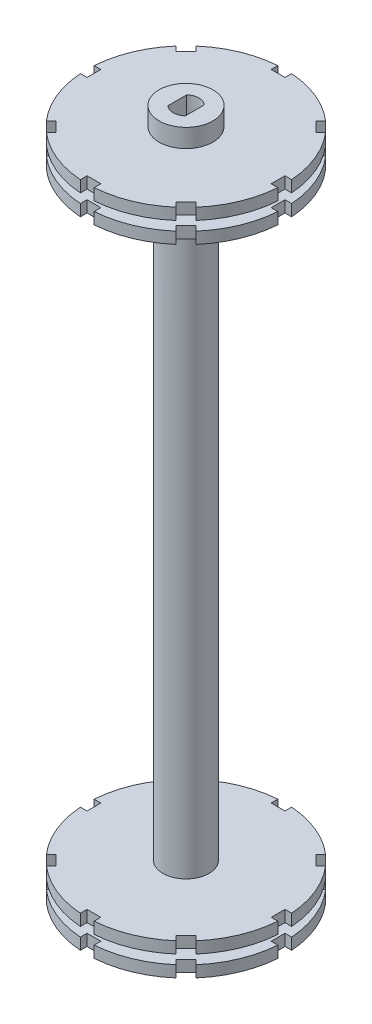
SolidWorks part; units mm, degrees
note: '?' marks a value the reader was unsure of.
ref_plane "Front Plane" through (0, 0, 0) normal (0, 0, 1) x (1, 0, 0)
ref_plane "Top Plane" through (0, 0, 0) normal (0, 1, 0) x (1, 0, 0)
ref_plane "Right Plane" through (0, 0, 0) normal (1, 0, 0) x (0, 0, -1)
sketch "Sketch1" plane through (0, 0, 0) normal (0, 1, 0) x (1, 0, 0)
  line L0 (1.9, 2.0567) -> (1.9, -2.0567)
  line L1 (-1.9, -2.0567) -> (-1.9, 2.0567)
  line L2 (-1.9, 2.0567) -> (-1.9, 5.5329)
  line L3 (1.9, 2.0567) -> (1.9, 5.5329)
  line L4 (-1.9, -2.0567) -> (-1.9, -5.5329)
  line L5 (1.9, -2.0567) -> (1.9, -5.5329)
  circle A0 centre (0, 0) radius 2.8
  circle A1 centre (0, 0) radius 5.85
  dimension "D1" = 5.6
  dimension "D4" = 11.7
  dimension "D2" = 1.9
  dimension "D3" = 1.9
extrude "Boss-Extrude1" add sketch "Sketch1" along normal blind 6.5 contours L2 A1 L4 A0 | L3 A1 L2 A0 | L5 A1 L3 A0 | L4 A1 L5 A0 | L1 A0 | L0 A0
sketch "Sketch2" plane through (0, 6.5, 0) normal (0, 1, 0) x (1, 0, 0)
  circle A0 centre (0, 0) radius 21.5
  dimension "D1" = 43
extrude "Boss-Extrude2" add sketch "Sketch2" against normal blind 2.5
sketch "Sketch3" plane through (0, 4, 0) normal (0, -1, 0) x (1, 0, 0)
  line L2 (-1.9, 2.0567) -> (-1.9, -2.0567)
  line L3 (1.9, -2.0567) -> (1.9, 2.0567)
  line L4 (-1.9, 2.0567) -> (-1.9, -2.0567)
  line L5 (1.9, -2.0567) -> (1.9, 2.0567)
  arc A2 (1.9, 2.0567) -> (-1.9, 2.0567) centre (0, 0) ccw
  arc A3 (-1.9, -2.0567) -> (1.9, -2.0567) centre (0, 0) ccw
  arc A4 (1.9, 2.0567) -> (-1.9, 2.0567) centre (0, 0) ccw
  arc A5 (-1.9, -2.0567) -> (1.9, -2.0567) centre (0, 0) ccw
  dimension "D1" = 0
extrude "Cut-Extrude1" cut sketch "Sketch3" against normal blind 8
sketch "Sketch4" plane through (0, 6.5, 0) normal (0, 1, 0) x (1, 0, 0)
  line L5 (15.2028, -13.0815) -> (17.3241, -15.2028)
  line L6 (15.2028, -13.0815) -> (13.0815, -15.2028)
  line L9 (20, 1.5) -> (23, 1.5)
  line L10 (20, 1.5) -> (20, -1.5)
  line L11 (20, -1.5) -> (23, -1.5)
  line L12 (23, 1.5) -> (23, -1.5)
  line L13 (20, 1.5) -> (23, -1.5) construction
  line L14 (20, -1.5) -> (23, 1.5) construction
  line L36 (13.0815, -15.2028) -> (15.2028, -17.3241)
  line L41 (17.3241, -15.2028) -> (15.2028, -17.3241)
  line L42 (15.2028, -13.0815) -> (15.2028, -17.3241) construction
  line L47 (13.0815, -15.2028) -> (17.3241, -15.2028) construction
  line L48 (1.5, -20) -> (1.5, -23)
  line L49 (1.5, -20) -> (-1.5, -20)
  line L54 (-1.5, -20) -> (-1.5, -23)
  line L55 (1.5, -23) -> (-1.5, -23)
  line L56 (1.5, -20) -> (-1.5, -23) construction
  line L61 (-1.5, -20) -> (1.5, -23) construction
  line L62 (-13.0815, -15.2028) -> (-15.2028, -17.3241)
  line L63 (-13.0815, -15.2028) -> (-15.2028, -13.0815)
  line L68 (-15.2028, -13.0815) -> (-17.3241, -15.2028)
  line L69 (-15.2028, -17.3241) -> (-17.3241, -15.2028)
  line L70 (-13.0815, -15.2028) -> (-17.3241, -15.2028) construction
  line L71 (-15.2028, -13.0815) -> (-15.2028, -17.3241) construction
  line L72 (-20, -1.5) -> (-23, -1.5)
  line L73 (-20, -1.5) -> (-20, 1.5)
  line L74 (-20, 1.5) -> (-23, 1.5)
  line L75 (-23, -1.5) -> (-23, 1.5)
  line L76 (-20, -1.5) -> (-23, 1.5) construction
  line L77 (-20, 1.5) -> (-23, -1.5) construction
  line L78 (-15.2028, 13.0815) -> (-17.3241, 15.2028)
  line L79 (-15.2028, 13.0815) -> (-13.0815, 15.2028)
  line L80 (-13.0815, 15.2028) -> (-15.2028, 17.3241)
  line L81 (-17.3241, 15.2028) -> (-15.2028, 17.3241)
  line L82 (-15.2028, 13.0815) -> (-15.2028, 17.3241) construction
  line L83 (-13.0815, 15.2028) -> (-17.3241, 15.2028) construction
  line L84 (-1.5, 20) -> (-1.5, 23)
  line L85 (-1.5, 20) -> (1.5, 20)
  line L86 (1.5, 20) -> (1.5, 23)
  line L87 (-1.5, 23) -> (1.5, 23)
  line L88 (-1.5, 20) -> (1.5, 23) construction
  line L89 (1.5, 20) -> (-1.5, 23) construction
  line L90 (13.0815, 15.2028) -> (15.2028, 17.3241)
  line L91 (13.0815, 15.2028) -> (15.2028, 13.0815)
  line L92 (15.2028, 13.0815) -> (17.3241, 15.2028)
  line L93 (15.2028, 17.3241) -> (17.3241, 15.2028)
  line L94 (13.0815, 15.2028) -> (17.3241, 15.2028) construction
  line L95 (15.2028, 13.0815) -> (15.2028, 17.3241) construction
  circle A0 centre (0, 0) radius 21.5 construction
  point P2 (15.2028, -15.2028)
  point P8 (0, -21.5)
  point P12 (21.5, 0)
  point P19 (-15.2028, -15.2028)
  point P24 (-21.5, 0)
  point P29 (-15.2028, 15.2028)
  point P34 (0, 21.5)
  point P39 (15.2028, 15.2028)
  dimension "D1" = 8
  dimension "D4" = 3
  dimension "D5" = 3
ref_axis "Axis1" through (0, 6.5, 0) along (0, -1, 0)?
extrude "Cut-Extrude2" cut sketch "Sketch4" against normal blind 10
sketch "Sketch5" plane through (0, 6.5, 0) normal (0, 1, 0) x (1, 0, 0)
  circle A0 centre (0, 0) radius 5
  dimension "D1" = 10
extrude "Boss-Extrude3" add sketch "Sketch5" along normal blind 140
ref_plane "Plane1" through (0, 76.5, 0) normal (0, 1, 0) x (1, 0, 0)
mirror "Mirror1" about plane through (0, 76.5, 0) normal (0, 1, 0) of "Boss-Extrude2"
mirror "Mirror2" about plane through (0, 76.5, 0) normal (0, 1, 0) of "Boss-Extrude1"
ref_plane "Plane2" through (0, 7.5, 0) normal (0, 1, 0) x (1, 0, 0)
mirror "Mirror3" about plane through (0, 7.5, 0) normal (0, 1, 0) of "Cut-Extrude2", "Boss-Extrude2", "Cut-Extrude1"
sketch "Sketch6" plane through (0, 11, 0) normal (0, -1, 0) x (1, 0, 0)
  line L2 (-1.9, 2.0567) -> (-1.9, -2.0567)
  line L3 (1.9, -2.0567) -> (1.9, 2.0567)
  line L4 (-1.9, 2.0567) -> (-1.9, -2.0567)
  line L5 (1.9, -2.0567) -> (1.9, 2.0567)
  arc A2 (1.9, 2.0567) -> (-1.9, 2.0567) centre (0, 0) ccw
  arc A3 (-1.9, -2.0567) -> (1.9, -2.0567) centre (0, 0) ccw
  arc A4 (1.9, 2.0567) -> (-1.9, 2.0567) centre (0, 0) ccw
  arc A5 (-1.9, -2.0567) -> (1.9, -2.0567) centre (0, 0) ccw
  dimension "D1" = 0
extrude "Cut-Extrude3" cut sketch "Sketch6" against normal blind 15
ref_plane "Plane3" through (0, 145.5, 0) normal (0, -1, 0) x (-1, 0, 0)
mirror "Mirror5" about plane through (0, 76.5, 0) normal (0, 1, 0) of "Cut-Extrude2"
mirror "Mirror6" about plane through (0, 145.5, 0) normal (0, -1, 0) of "Mirror5", "Mirror1"
sketch "Sketch7" plane through (0, 153, 0) normal (0, 1, 0) x (1, 0, 0)
